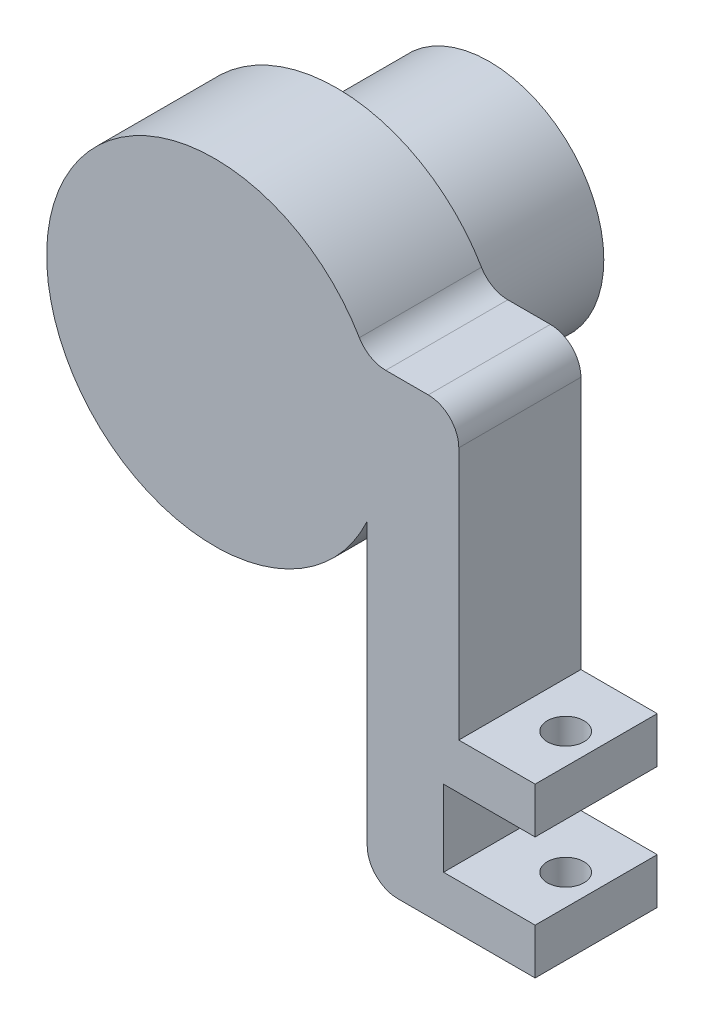
SolidWorks part; units mm, degrees
ref_plane "Plan de face" through (0, 0, 0) normal (0, 0, 1) x (1, 0, 0)
ref_plane "Plan de dessus" through (0, 0, 0) normal (0, 1, 0) x (1, 0, 0)
ref_plane "Plan de droite" through (0, 0, 0) normal (1, 0, 0) x (0, 0, -1)
sketch "Esquisse1" plane through (0, 0, 0) normal (0, 0, 1) x (1, 0, 0)
  line L1 (0, 0) -> (32, 0) construction
  line L2 (0, 0) -> (0, -36) construction
  line L3 (0, -36) -> (32, -36) construction
  line L4 (32, 0) -> (32, -36) construction
  line L5 (21, -6.4174) -> (27, -6.4174)
  line L7 (27, -6.4174) -> (27, -25)
  line L8 (32, -28) -> (32, -25)
  line L9 (32, -36) -> (21, -36)
  line L10 (32, -36) -> (32, -33)
  line L11 (32, -25) -> (27, -25)
  line L14 (21, -36) -> (21, -15.5826)
  line L17 (32, -33) -> (26, -33)
  line L19 (32, -28) -> (26, -28)
  line L20 (26, -33) -> (26, -28)
  line L21 (21, -6.4174) -> (21, -15.5826) construction
  arc A0 (21, -6.4174) -> (21, -15.5826) centre (11, -11) ccw
  point P6 (21, -11)
  point P20 (26, -30.5)
  dimension "D3" = 22
  dimension "D1" = 32
  dimension "D2" = 36
  dimension "D4" = 11
  dimension "D5" = 11
  dimension "D6" = 11
  dimension "D8" = 6
  dimension "D9" = 5
  dimension "D10" = 5.5
  dimension "D11" = 5
  dimension "D7" = 21
extrude "Boss.-Extru.1" add sketch "Esquisse1" along normal blind 8
sketch "Esquisse2" plane through (0, -25, 0) normal (0, 1, 0) x (1, 0, 0)
  line L0 (27, -8) -> (27, 0) construction
  line L1 (32, -8) -> (27, -8) construction
  circle A0 centre (30, -4) radius 1
  dimension "D1" = 2
  dimension "D2" = 3
  dimension "D3" = 4
extrude "Enlèv. mat.-Extru.1" cut sketch "Esquisse2" against normal up to surface (11 mm away) up to face at (26.5, -36, 4)
hole_wizard "Dégagement M21" positions "Esquisse3" profile "Esquisse4" hole size "M2" standard "ISO"
sketch "Esquisse3" plane through (0, -25, 0) normal (0, 1, 0) x (1, 0, 0)
  point P0 (30, -4)
sketch "Esquisse4" plane through (30, -25, 4) normal (1, 0, 0) x (0, 0, 1)
  line L0 (0, 0) -> (0, 11.721)
  line L1 (0, 11.721) -> (1.2, 11)
  line L2 (1.2, 11) -> (1.2, 0)
  line L5 (1.2, 0) -> (0, 0)
  line L10 (0, 11.721) -> (-1.2, 11) construction
  line L11 (0, -6.35) -> (0, 107.95) construction
  dimension "Diamètre du perçage" = 2.4
  dimension "Profondeur du perçage" = 11
  dimension "Angle de pointe" = 118
fillet "Congé1" radius 2 3 edges at (21, -36, 4) (21, -6.4174, 4) (27, -6.4174, 4)
sketch "Esquisse5" plane through (0, 0, 8) normal (0, 0, 1) x (1, 0, 0)
  circle A0 centre (11, -11) radius 7.5
  dimension "D1" = 15
extrude "Boss.-Extru.2" [suppressed] add sketch "Esquisse5" along normal blind 10
sketch "Esquisse6" plane through (0, 0, 0) normal (0, 0, -1) x (-1, 0, 0)
  circle A0 centre (-11, -11) radius 7.5
  dimension "D1" = 15
extrude "Boss.-Extru.3" add sketch "Esquisse6" along normal blind 10
equation "\"D4@Esquisse1\"=\"D3@Esquisse1\"/2"
equation "\"D5@Esquisse1\"=\"D3@Esquisse1\"/2"
equation "\"D10@Esquisse1\"=\"D6@Esquisse1\"/2"
